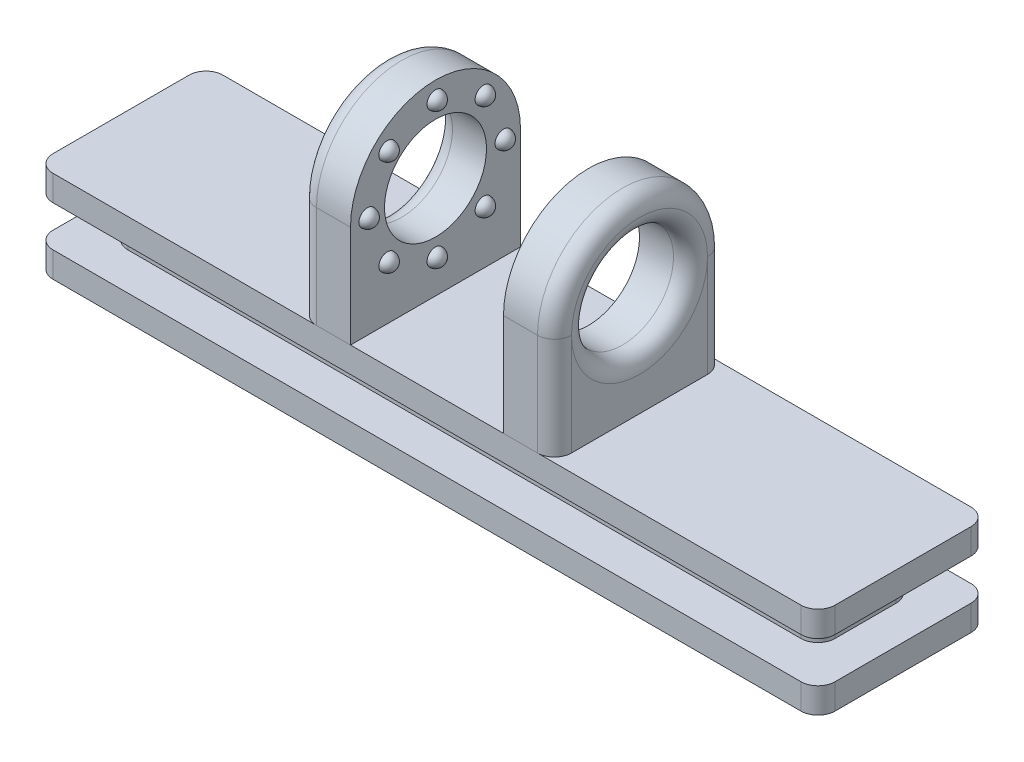
SolidWorks part; units mm, degrees
ref_plane "Front Plane" through (0, 0, 0) normal (0, 0, 1) x (1, 0, 0)
ref_plane "Top Plane" through (0, 0, 0) normal (0, 1, 0) x (1, 0, 0)
ref_plane "Right Plane" through (0, 0, 0) normal (1, 0, 0) x (0, 0, -1)
sketch "Sketch1" plane through (0, 0, 0) normal (0, 1, 0) x (1, 0, 0)
  line L0 (0, -1.5865) -> (0, -28.9135) construction
  line L1 (23, -25.25) -> (-23, -25.25)
  line L2 (23, -25.25) -> (23, -15.25)
  line L3 (23, -15.25) -> (-23, -15.25)
  line L4 (-23, -25.25) -> (-23, -15.25)
  line L5 (-26.4896, -20.25) -> (-19.5104, -20.25) construction
  point P4 (0, -15.25)
  point P5 (-23, -20.25)
  dimension "D1" = 46
  dimension "D2" = 10
extrude "Boss-Extrude1" add sketch "Sketch1" along normal blind 1.5 separate body
fillet "Fillet6" radius 1 4 edges at (-23, 0.75, 25.25) (-23, 0.75, 15.25) (23, 0.75, 15.25) (23, 0.75, 25.25)
ref_plane "Plane5" through (0, -1.2, 0) normal (0, 1, 0) x (1, 0, 0)
ref_plane "Plane6" through (4.5, 0, 0) normal (1, 0, 0) x (0, 0, -1)
mirror "Mirror2" about plane through (0, -1.2, 0) normal (0, 1, 0) of bodies 102
sketch "Sketch2" plane through (0, 0, 0) normal (0, 1, 0) x (1, 0, 0)
  line L0 (20.8, -17.45) -> (-20.8, -17.45)
  line L1 (23, -15.25) -> (-23, -15.25) construction
  line L2 (23, -15.25) -> (23, -25.25) construction
  line L3 (23, -25.25) -> (-23, -25.25) construction
  line L4 (-23, -15.25) -> (-23, -25.25) construction
  line L5 (-20.8, -17.45) -> (-20.8, -23.05)
  line L6 (20.8, -23.05) -> (-20.8, -23.05)
  line L7 (20.8, -17.45) -> (20.8, -23.05)
  line L8 (0, 0) -> (0, -31.754) construction
  point P11 (0, -25.25)
  dimension "D1" = 2.2
extrude "Boss-Extrude2" add sketch "Sketch2" against normal up to next
sketch "Sketch3" plane through (4.5, 0, 0) normal (1, 0, 0) x (0, 0, -1)
  line L0 (-24.25, 1.5) -> (-16.25, 1.5) construction
  line L1 (-20.25, 20.9216) -> (-20.25, -5.9216) construction
  line L2 (-15.25, 1.5) -> (-15.25, 0) construction
  line L3 (-25.25, 7.5) -> (-25.25, 1.5)
  line L4 (-25.25, 1.5) -> (-15.25, 1.5)
  line L5 (-15.25, 1.5) -> (-15.25, 7.5)
  arc A1 (-15.25, 7.5) -> (-25.25, 7.5) centre (-20.25, 7.5) ccw
  point P14 (-15.2582, 7.5)
  dimension "D1" = 10
  dimension "D2" = 5
  dimension "D3" = 6
  dimension "D4" = 5
extrude "Boss-Extrude4" add sketch "Sketch3" along normal blind 3 separate body
sketch "Sketch5" plane through (0, 0, 0) normal (1, 0, 0) x (0, 0, -1)
  line L0 (-20.25, 14.209) -> (-20.25, -7.0256) construction
  circle A0 centre (-20.25, 7.5) radius 3
  dimension "D1" = 6
extrude "Cut-Extrude1" cut sketch "Sketch5" along normal up to next
sketch "Sketch4" plane through (4.5, 0, 0) normal (1, 0, 0) x (0, 0, -1)
  line L0 (-20.25, 6.4178) -> (-20.25, 13.0948) construction
  line L1 (-20.25, 11.0034) -> (-20.25, 12.0034)
  arc A0 (-20.25, 11.0034) -> (-20.25, 12.0034) centre (-20.25, 11.5034) ccw
  circle A1 centre (-20.25, 7.5) radius 4.0034 construction
revolve "Revolve1" add sketch "Sketch4" angle 360 about L0
pattern_circular "CirPattern1" count 8 over 360 about axis through (0, 7.5, 20.25) along (1, 0, 0) of "Revolve1"
mirror "Mirror4" about plane through (0, 0, 0) normal (1, 0, 0) of bodies 109
fillet "Fillet1" radius 1 4 edges at (-20.8, -1.2, 23.05) (-20.8, -1.2, 17.45) (20.8, -1.2, 23.05) (20.8, -1.2, 17.45)
fillet "Fillet2" radius 1 3 edges at (7.5, 4.5, 15.25) (7.5, 12.5, 20.25) (7.5, 4.5, 25.25)
fillet "Fillet3" radius 1 1 edges at (7.5, 7.5, 17.25)
fillet "Fillet4" radius 1 3 edges at (-7.5, 4.5, 25.25) (-7.5, 12.5, 20.25) (-7.5, 4.5, 15.25)
fillet "Fillet5" radius 1 1 edges at (-7.5, 7.5, 17.25)
